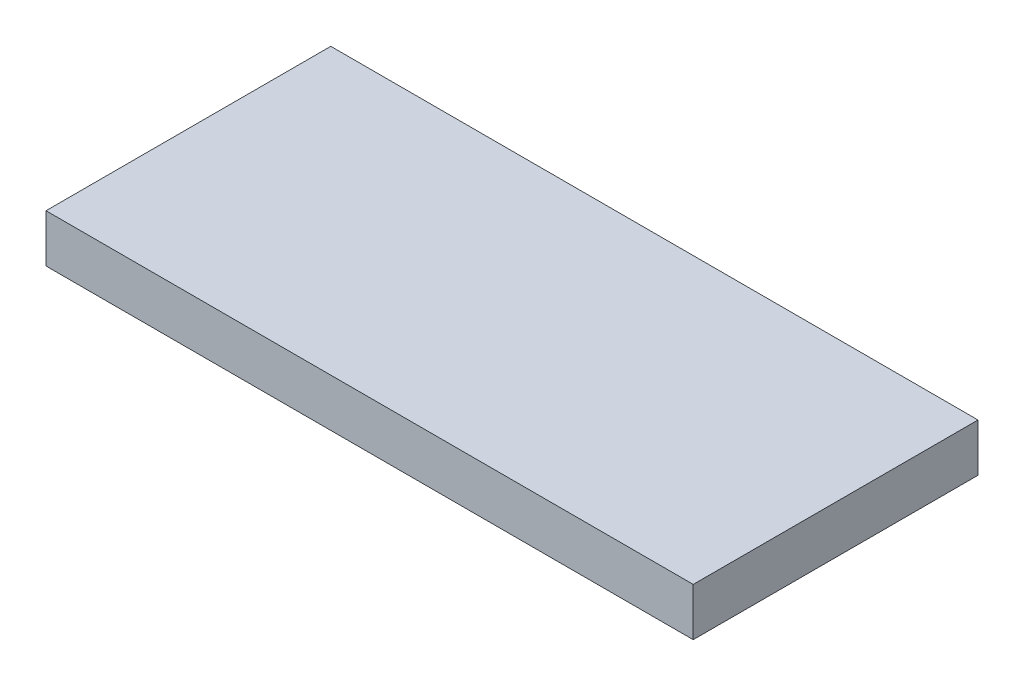
SolidWorks part; units mm, degrees
ref_plane "Front Plane" through (0, 0, 0) normal (0, 0, 1) x (1, 0, 0)
ref_plane "Top Plane" through (0, 0, 0) normal (0, 1, 0) x (1, 0, 0)
ref_plane "Right Plane" through (0, 0, 0) normal (1, 0, 0) x (0, 0, -1)
sketch "Clips Outline" plane through (0, 0, 0) normal (0, 0, 1) x (1, 0, 0)
  line L0 (6.35, 3.7592) -> (5.327, 4.699)
  line L1 (-6.35, 0) -> (-6.35, 3.7592)
  line L2 (6.35, 4.699) -> (6.35, 6.5837)
  line L3 (-6.35, 6.5837) -> (-7.2898, 6.5837)
  line L4 (-7.2898, 6.5837) -> (-7.2898, -0.9398)
  line L5 (-7.2898, -0.9398) -> (-6.35, -0.9398)
  line L6 (-6.35, 0) -> (-6.35, -0.9398)
  line L7 (-6.35, 4.699) -> (-5.327, 4.699)
  line L8 (-6.35, 4.699) -> (-6.35, 6.5837)
  line L9 (-6.35, 3.7592) -> (-5.327, 4.699)
  line L10 (0, 0) -> (0, 10.8923) construction
  line L11 (6.35, 4.699) -> (5.327, 4.699)
  line L12 (6.35, 0) -> (6.35, -0.9398)
  line L13 (7.2898, -0.9398) -> (6.35, -0.9398)
  line L14 (7.2898, 6.5837) -> (7.2898, -0.9398)
  line L15 (6.35, 6.5837) -> (7.2898, 6.5837)
  line L16 (6.35, 0) -> (6.35, 3.7592)
  point P3 (0, 0)
  dimension "D1" = 6.35
sketch "Base Outline Adhesive" plane through (0, 0, 0) normal (0, 0, 1) x (1, 0, 0)
  line L0 (6.35, 0) -> (-6.35, 0)
  line L1 (-6.35, -0.9398) -> (6.35, -0.9398)
  line L2 (6.35, -0.9398) -> (6.35, 0)
  line L3 (-6.35, 0) -> (-6.35, -0.9398)
  point P3 (0, 0)
extrude "Self Adhesive Base" add sketch "Base Outline Adhesive" along normal mid plane 5.588
ref_plane "Plane1" through (0, 1, 0) normal (0, 1, 0) x (-1, 0, 0)
sketch "Sketch1" plane through (0, 1, 0) normal (0, 1, 0) x (-1, 0, 0)
  line L0 (0, -2.794) -> (0, 2.794)
ref_axis "Clip Axis" through (0, 1, -2.794) along (0, 0, 1)
ref_axis "Axis of Rotation" through (0, 0, 0) along (0, 1, 0)
equation "\"D1@Clips Outline\" = \"Base_Width@Base Outline Adhesive\"/2"
